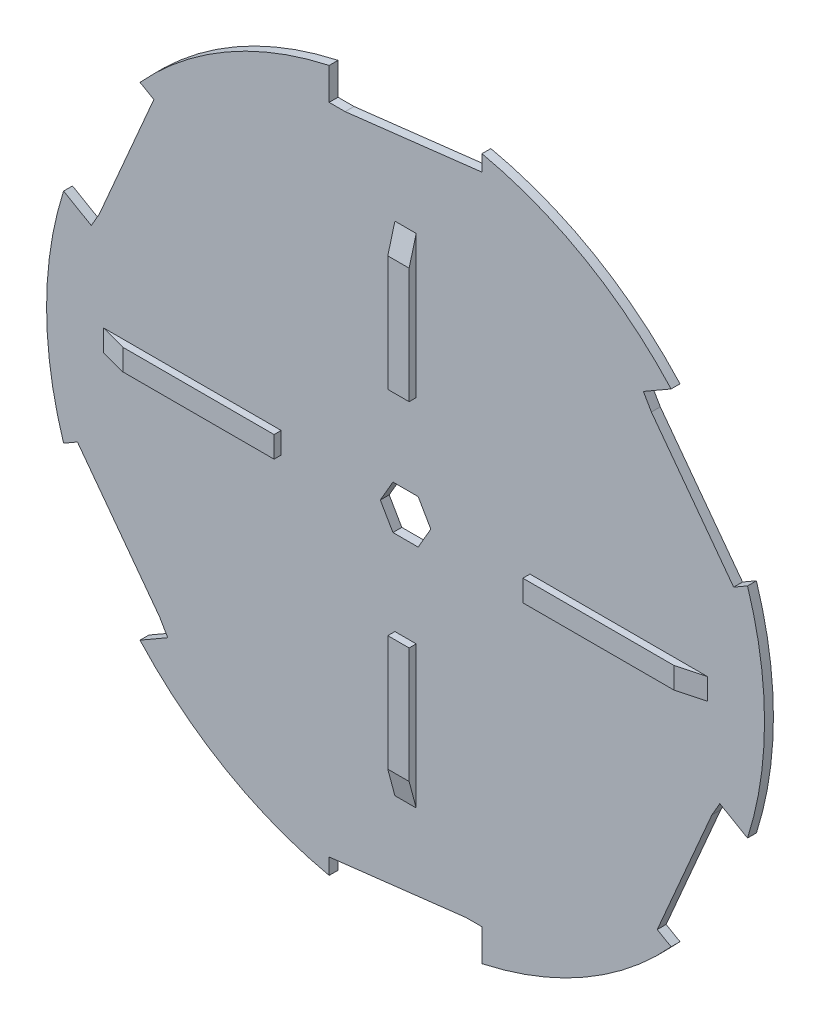
SolidWorks part; units mm, degrees
ref_plane "Front Plane" through (0, 0, 0) normal (0, 0, 1) x (1, 0, 0)
ref_plane "Top Plane" through (0, 0, 0) normal (0, 1, 0) x (1, 0, 0)
ref_plane "Right Plane" through (0, 0, 0) normal (1, 0, 0) x (0, 0, -1)
sketch "Sketch1" plane through (0, 0, 0) normal (0, 0, 1) x (1, 0, 0)
  circle A0 centre (0, 0) radius 101
  dimension "D1" = 202
extrude "Boss-Extrude1" add sketch "Sketch1" along normal blind 2.5 contours A0
sketch "Sketch8" plane through (0, 0, 0) normal (0, 0, -1) x (-1, 0, 0)
  text T0 "02-04-141118"
extrude "Cut-Extrude6" cut sketch "Sketch8" against normal blind 0.2
sketch "Sketch9" plane through (0, 0, 2.5) normal (0, 0, 1) x (1, 0, 0)
  line L1 (-7.1014, 0) -> (-3.5507, -6.15)
  line L2 (-3.5507, -6.15) -> (3.5507, -6.15)
  line L3 (3.5507, -6.15) -> (7.1014, 0)
  line L4 (7.1014, 0) -> (3.5507, 6.15)
  line L5 (3.5507, 6.15) -> (-3.5507, 6.15)
  line L6 (-3.5507, 6.15) -> (-7.1014, 0)
  circle A0 centre (0, 0) radius 6.15 construction
  dimension "D1" = 12.3
extrude "Cut-Extrude7" cut sketch "Sketch9" against normal blind 10
sketch "Sketch11" plane through (0, 0, 2.5) normal (0, 0, 1) x (1, 0, 0)
  line L0 (0, 0) -> (-85, 0)
  line L1 (-85, 0) -> (-85, 3)
  line L2 (-85, 3) -> (-35, 3)
  line L3 (-35, 3) -> (-35, -3)
  line L4 (-35, -3) -> (-85, -3)
  line L5 (-85, -3) -> (-85, 0)
  line L6 (0, 0) -> (0, 70)
  line L7 (0, 70) -> (-3, 70)
  line L8 (-3, 70) -> (-3, 30)
  line L9 (-3, 30) -> (3, 30)
  line L10 (3, 30) -> (3, 70)
  line L11 (3, 70) -> (0, 70)
  line L12 (35, 3) -> (85, 3)
  line L13 (35, -3) -> (35, 3)
  line L14 (85, -3) -> (35, -3)
  line L15 (85, 3) -> (85, 0)
  line L16 (85, 0) -> (85, -3)
  line L17 (3, -30) -> (-3, -30)
  line L18 (3, -70) -> (3, -30)
  line L19 (-3, -30) -> (-3, -70)
  line L20 (0, -70) -> (3, -70)
  line L21 (-3, -70) -> (0, -70)
  point P20 (0, 0)
  point P26 (0, 0)
  dimension "D1" = 3
  dimension "D2" = 6
  dimension "D3" = 6
  dimension "D4" = 3
  dimension "D5" = 85
  dimension "D6" = 50
  dimension "D7" = 70
  dimension "D8" = 40
  dimension "D9" = 2
  dimension "D10" = 2
extrude "Boss-Extrude2" add sketch "Sketch11" along normal blind 2 contours L7 L8 L9 L10 L11 | L1 L2 L3 L4 L5 | L14 L13 L12 L15 L16 | L19 L21 L20 L18 L17
chamfer "Chamfer1" distance 2 angle 75 4 edges at (85, 0, 4.5) (0, 70, 4.5) (0, -70, 4.5) (-85, 0, 4.5)
sketch "Sketch13" plane through (0, 0, 2.5) normal (0, 0, 1) x (1, 0, 0)
  line L0 (-21.5, 98.6851) -> (-21.5, 106.676)
  line L1 (-21.5, 106.676) -> (21.5, 108.9525)
  line L2 (21.5, 94.1851) -> (21.5, 98.6851)
  line L3 (-17, 89.6851) -> (-21.5, 89.6851)
  line L4 (-21.5, 89.6851) -> (-21.5, 98.6851)
  line L5 (21.5, 94.1851) -> (-17, 89.6851)
  line L6 (21.5, 108.9525) -> (21.5, 98.6851)
  line L7 (74.7138, 67.9621) -> (81.6341, 71.9575)
  line L8 (66.9196, 63.4621) -> (74.7138, 67.9621)
  line L9 (69.1696, 59.565) -> (66.9196, 63.4621)
  line L10 (92.3167, 28.473) -> (69.1696, 59.565)
  line L11 (92.3167, 28.473) -> (96.2138, 30.723)
  line L12 (105.1056, 35.8567) -> (96.2138, 30.723)
  line L13 (81.6341, 71.9575) -> (105.1056, 35.8567)
  line L14 (96.2138, -30.723) -> (103.1341, -34.7184)
  line L15 (88.4196, -26.223) -> (96.2138, -30.723)
  line L16 (86.1696, -30.1201) -> (88.4196, -26.223)
  line L17 (70.8167, -65.7121) -> (86.1696, -30.1201)
  line L18 (70.8167, -65.7121) -> (74.7138, -67.9621)
  line L19 (83.6056, -73.0958) -> (74.7138, -67.9621)
  line L20 (103.1341, -34.7184) -> (83.6056, -73.0958)
  line L21 (21.5, -98.6851) -> (21.5, -106.676)
  line L22 (21.5, -89.6851) -> (21.5, -98.6851)
  line L23 (17, -89.6851) -> (21.5, -89.6851)
  line L24 (-21.5, -94.1851) -> (17, -89.6851)
  line L25 (-21.5, -94.1851) -> (-21.5, -98.6851)
  line L26 (-21.5, -108.9525) -> (-21.5, -98.6851)
  line L27 (21.5, -106.676) -> (-21.5, -108.9525)
  line L28 (-74.7138, -67.9621) -> (-81.6341, -71.9575)
  line L29 (-66.9196, -63.4621) -> (-74.7138, -67.9621)
  line L30 (-69.1696, -59.565) -> (-66.9196, -63.4621)
  line L31 (-92.3167, -28.473) -> (-69.1696, -59.565)
  line L32 (-92.3167, -28.473) -> (-96.2138, -30.723)
  line L33 (-105.1056, -35.8567) -> (-96.2138, -30.723)
  line L34 (-81.6341, -71.9575) -> (-105.1056, -35.8567)
  line L35 (-96.2138, 30.723) -> (-103.1341, 34.7184)
  line L36 (-88.4196, 26.223) -> (-96.2138, 30.723)
  line L37 (-86.1696, 30.1201) -> (-88.4196, 26.223)
  line L38 (-70.8167, 65.7121) -> (-86.1696, 30.1201)
  line L39 (-70.8167, 65.7121) -> (-74.7138, 67.9621)
  line L40 (-83.6056, 73.0958) -> (-74.7138, 67.9621)
  line L41 (-103.1341, 34.7184) -> (-83.6056, 73.0958)
  point P46 (0, 0)
  dimension "D2" = 6
  dimension "D5" = 9
  dimension "D6" = 4.5
extrude "Cut-Extrude9" cut sketch "Sketch13" against normal blind 10
equation "\"1.5.00mm\"=3"
